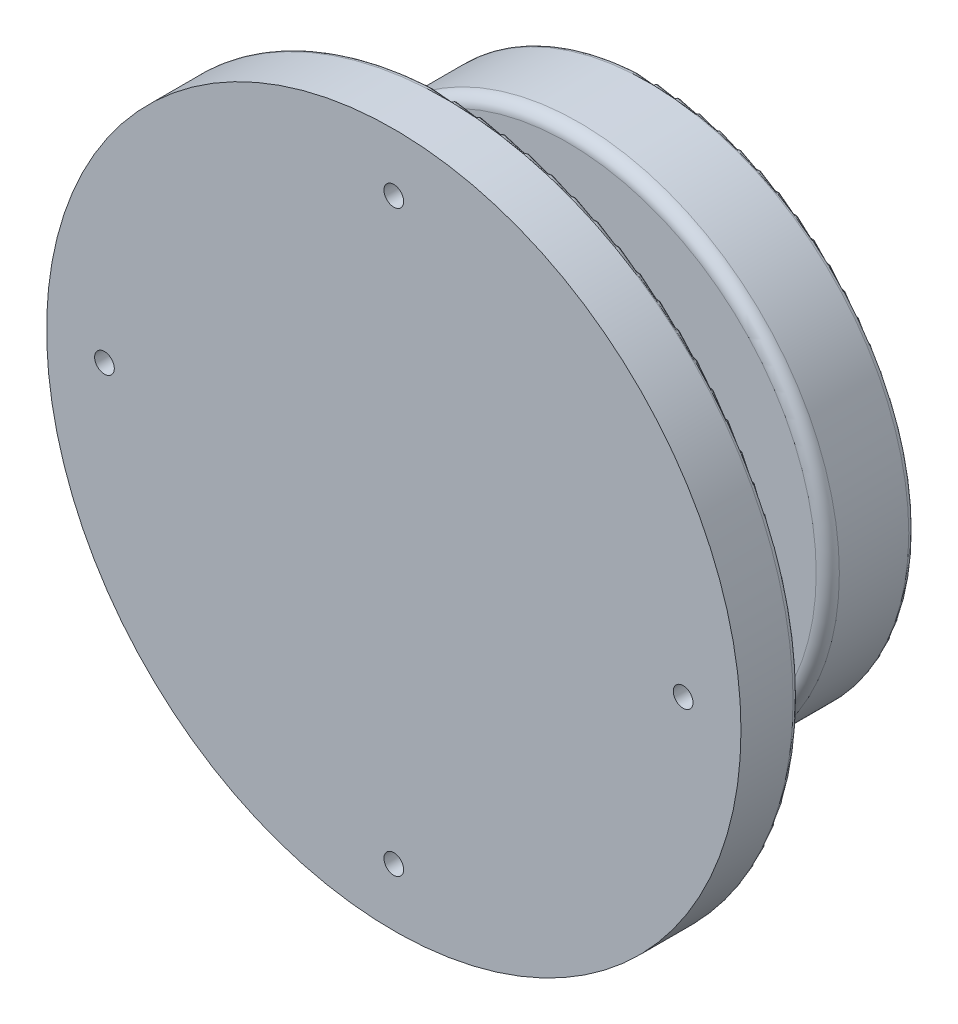
SolidWorks part; units mm, degrees
ref_plane "Plan de face" through (0, 0, 0) normal (0, 0, 1) x (1, 0, 0)
ref_plane "Plan de dessus" through (0, 0, 0) normal (0, 1, 0) x (1, 0, 0)
ref_plane "Plan de droite" through (0, 0, 0) normal (1, 0, 0) x (0, 0, -1)
sketch "Esquisse1" plane through (0, 0, 0) normal (0, 0, 1) x (1, 0, 0)
  circle A0 centre (0, 0) radius 45
  dimension "D1" = 90
extrude "Boss.-Extru.1" add sketch "Esquisse1" along normal blind 15
sketch "Esquisse3" plane through (0, 0, 15) normal (0, 0, 1) x (1, 0, 0)
  circle A0 centre (0, 0) radius 10
  dimension "D1" = 20
extrude "Boss.-Extru.2" add sketch "Esquisse3" along normal blind 20
sketch "Esquisse4" plane through (0, 0, 35) normal (0, 0, 1) x (1, 0, 0)
  circle A0 centre (0, 0) radius 60
  dimension "D1" = 120
extrude "Boss.-Extru.3" add sketch "Esquisse4" along normal blind 10
fillet "Congé1" radius 2 1 edges at (45, 0, 15)
sketch "Esquisse5" plane through (0, 0, 0) normal (0, 0, -1) x (-1, 0, 0)
  line L1 (-11.6, -2) -> (11.6, -2)
  line L2 (-11.6, -2) -> (-11.6, -33.8)
  line L3 (-11.6, -33.8) -> (11.6, -33.8)
  line L4 (11.6, -2) -> (11.6, -33.8)
  line L5 (-11.6, -2) -> (-11.6, 5.5)
  line L6 (11.6, -2) -> (11.6, 5.5)
  line L7 (-7.1, 10) -> (7.1, 10)
  arc A0 (-11.6, 5.5) -> (-7.1, 10) centre (-7.1, 5.5) cw
  arc A1 (7.1, 10) -> (11.6, 5.5) centre (7.1, 5.5) cw
  circle A2 centre (0, 0) radius 2.15
  dimension "D3" = 4.3
  dimension "D6" = 4.5
  dimension "D7" = 4.5
  dimension "D1" = 2
  dimension "D2" = 11.6
  dimension "D4" = 43.8
  dimension "D5" = 23.2
  dimension "D8" = 12
fillet "Congé2" radius 1 1 edges at (60, 0, 35)
fillet "Congé3" radius 1 1 edges at (45, 0, 0)
sketch "Esquisse6" plane through (0, 0, 0) normal (0, 0, 1) x (1, 0, 0)
  circle A0 centre (0, 0) radius 7
  circle A1 centre (7, 0) radius 1.25
  circle A2 centre (-7, 0) radius 1.25
  dimension "D1" = 14
  dimension "D2" = 2.5
hole_wizard "Trou taraudé M31" positions "Esquisse3D1" profile "Esquisse7" tap size "M3" standard "Iso"
sketch3d "Esquisse3D1"
  point P0 (-7, 0, 0)
  point P3 (7, 0, 0)
sketch "Esquisse7" plane through (-7, 0, 0) normal (1, 0, 0) x (0, 1, 0)
  line L0 (0, 0) -> (0, 13.2511)
  line L1 (0, 13.2511) -> (1.25, 12.5)
  line L2 (1.25, 12.5) -> (1.25, 0)
  line L5 (1.25, 0) -> (0, 0)
  line L10 (0, 13.2511) -> (-1.25, 12.5) construction
  line L11 (0, -6.35) -> (0, 107.95) construction
  dimension "Diamètre du trou pour taraudage" = 2.5
  dimension "Profondeur du trou pour taraudage" = 12.5
  dimension "Angle de pointe" = 118
cosmetic thread "Filetage de perçage1" parameters "D1"=10, "D2"=3
cosmetic thread "Filetage de perçage2" parameters "D1"=10, "D2"=3
sketch "Esquisse8" plane through (0, 0, 35) normal (0, 0, 1) x (1, 0, 0)
  circle A0 centre (0, 0) radius 50
  circle A1 centre (0, 50) radius 1.5
  circle A2 centre (50, 0) radius 1.5
  circle A3 centre (0, -50) radius 1.5
  circle A4 centre (-50, 0) radius 1.5
  dimension "D1" = 100
  dimension "D2" = 3
hole_wizard "Chambrage pour vis à tête hexagonale M31" positions "Esquisse3D2" profile "Esquisse9" counterbore size "M3" standard "Iso" end condition through all
sketch3d "Esquisse3D2"
  point P0 (0, 50, 35)
  point P3 (50, 0, 35)
  point P6 (0, -50, 35)
  point P9 (-50, 0, 35)
sketch "Esquisse9" plane through (0, 50, 35) normal (1, 0, 0) x (0, 1, 0)
  line L0 (0, 0) -> (0, 10)
  line L1 (0, 10) -> (1.7, 10)
  line L3 (1.7, 10) -> (1.7, 2)
  line L4 (4.6755, 2) -> (1.7, 2)
  line L5 (4.6755, 2) -> (4.6755, 0.025)
  line L6 (4.6755, 0.025) -> (4.7005, 0)
  line L7 (4.7005, 0) -> (0, 0)
  line L8 (-4.6755, 0.025) -> (-4.7005, 0) construction
  line L11 (0, -6.35) -> (0, 107.95) construction
  dimension "Diamètre du perçage jusqu'au prochain" = 3.4
  dimension "Profondeur du perçage jusqu'au prochain" = 10
  dimension "Diamètre du chambrage" = 9.351
  dimension "Profondeur du chambrage" = 2
  dimension "Diamètre du fraisage entrant" = 9.401
  dimension "Angle du fraisage entrant" = 90
